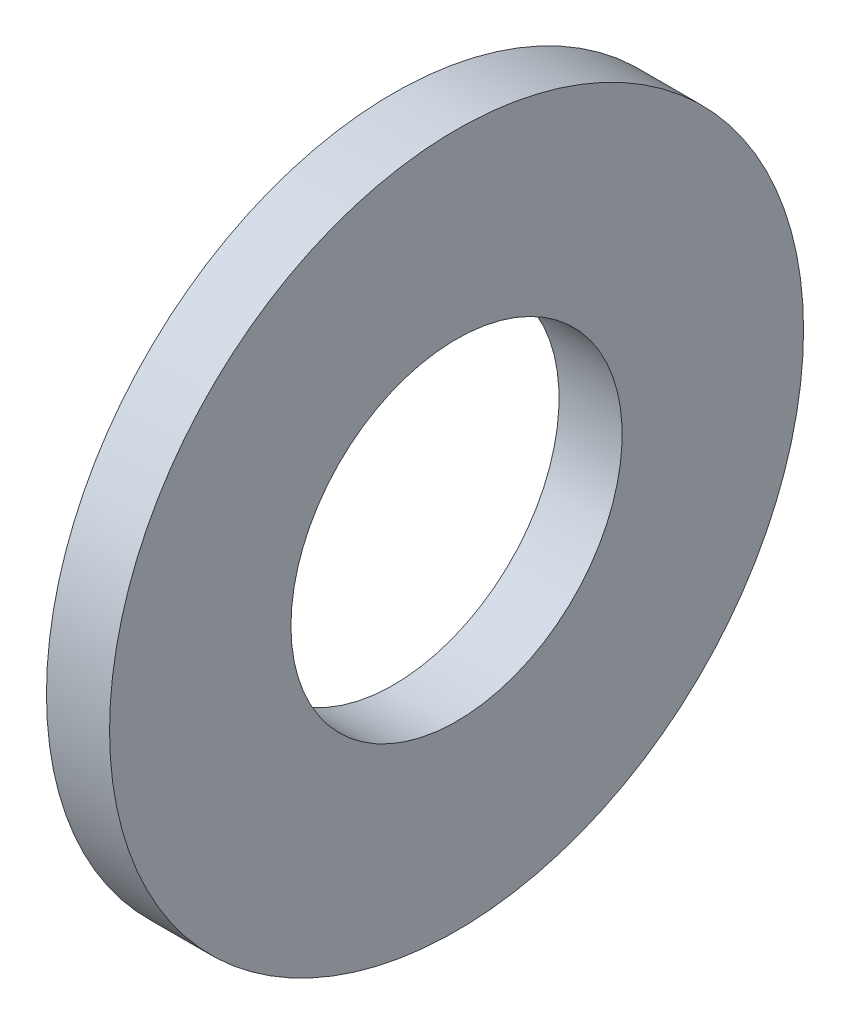
SolidWorks part; units mm, degrees
ref_plane "Plan1" through (0, 0, 0) normal (0, 0, 1) x (1, 0, 0)
ref_plane "Plan2" through (0, 0, 0) normal (0, 1, 0) x (1, 0, 0)
ref_plane "Plan3" through (0, 0, 0) normal (1, 0, 0) x (0, 0, -1)
sketch "Esquisse1" plane through (0, 0, 0) normal (0, 1, 0) x (1, 0, 0)
  line L0 (0, 0) -> (40, 0) construction
  line L2 (0, 11) -> (2, 11)
  line L3 (0, 11) -> (0, 5.25)
  line L4 (0, 5.25) -> (2, 5.25)
  line L5 (2, 11) -> (2, 5.25)
  dimension "D1" = 5.25
  dimension "D2" = 11
  dimension "D3" = 2
revolve "Base-Révolution" add sketch "Esquisse1" angle 360 about L0
ref_axis "Axe1" through (-50, 0, 0) along (1, 0, 0)
